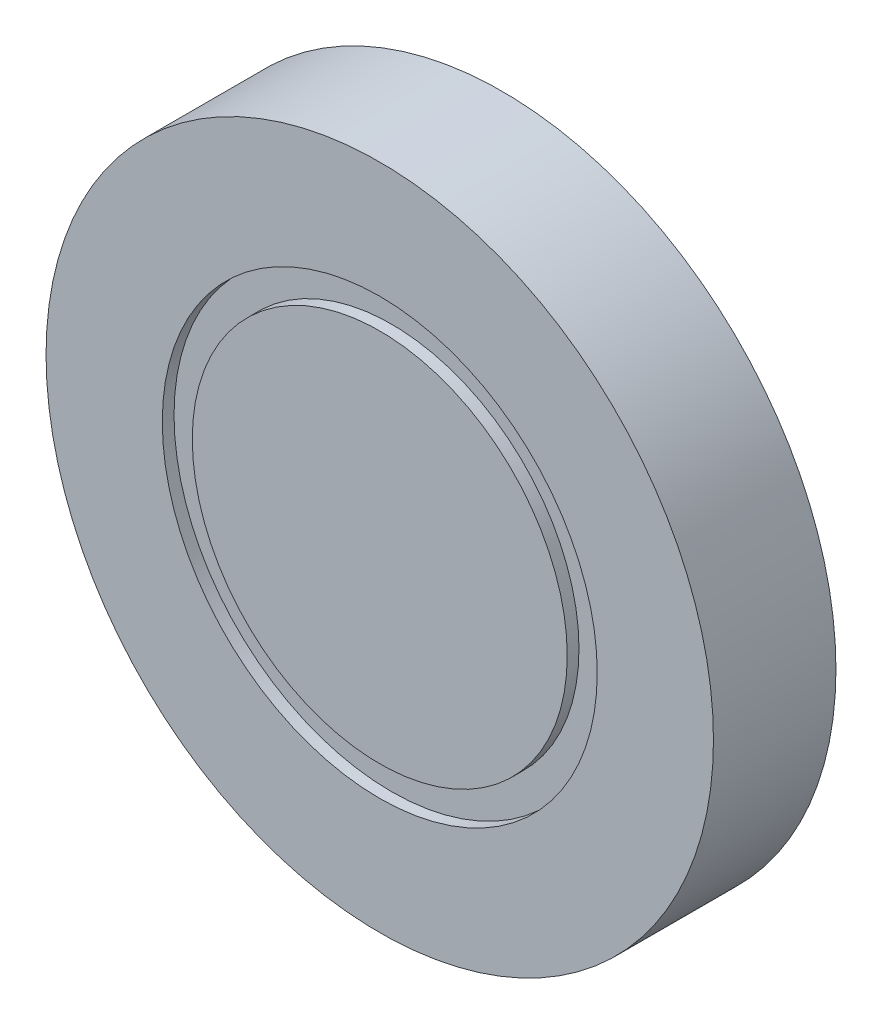
SolidWorks part; units mm, degrees
material "Bismuth"
ref_plane "Front" through (0, 0, 0) normal (0, 0, 1) x (1, 0, 0)
ref_plane "Top" through (0, 0, 0) normal (0, 1, 0) x (1, 0, 0)
ref_plane "Right" through (0, 0, 0) normal (1, 0, 0) x (0, 0, -1)
sketch "Sketch1" plane through (0, 0, 0) normal (0, 0, 1) x (1, 0, 0)
  circle A0 centre (0, 0) radius 133.5
  circle A1 centre (0, 0) radius 87
  circle A2 centre (0, 0) radius 75
extrude "Boss-Extrude1" add sketch "Sketch1" along normal blind 49 contours A2
extrude "Boss-Extrude2" add sketch "Sketch1<3>" along normal blind 44.3 contours A1 | A2
sketch "Sketch1<3>" plane through (0, 0, 0) normal (0, 0, 1) x (1, 0, 0) same geometry as "Sketch1"
extrude "Boss-Extrude3" add sketch "Sketch1<4>" along normal blind 49 contours A0 | A1
sketch "Sketch1<4>" plane through (0, 0, 0) normal (0, 0, 1) x (1, 0, 0) same geometry as "Sketch1"
